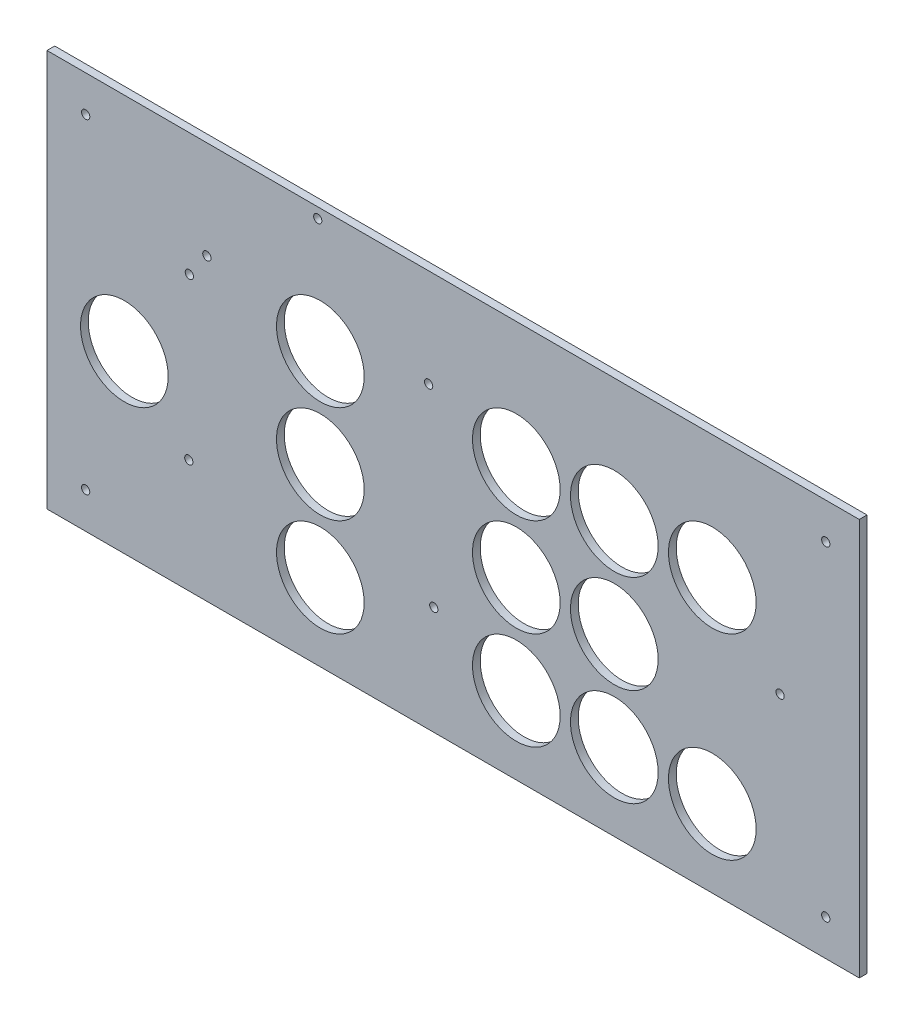
SolidWorks part; units mm, degrees
ref_plane "前视基准面" through (0, 0, 0) normal (0, 0, 1) x (1, 0, 0)
ref_plane "上视基准面" through (0, 0, 0) normal (0, 1, 0) x (1, 0, 0)
ref_plane "右视基准面" through (0, 0, 0) normal (1, 0, 0) x (0, 0, -1)
other "Configuration Table"
sketch "草图1" plane through (0, 0, 0) normal (0, 0, 1) x (1, 0, 0)
  line L1 (-150, -42) -> (165, -42)
  line L2 (-150, -42) -> (-150, 112)
  line L3 (-150, 112) -> (165, 112)
  line L4 (165, -42) -> (165, 112)
  line L5 (-150, -42) -> (165, 112) construction
  line L6 (-150, 112) -> (165, -42) construction
  circle A0 centre (0, 0) radius 1.6
  circle A1 centre (-94.8, 64.4) radius 1.6
  circle A2 centre (134.3, 38) radius 1.6
  circle A3 centre (-95, 2) radius 1.6
  circle A4 centre (-88, 74) radius 1.6
  circle A5 centre (-2, 74) radius 1.6
  circle A6 centre (-45, 108) radius 1.6
  circle A7 centre (-135, -28) radius 1.6
  circle A8 centre (152, -28) radius 1.6
  circle A9 centre (-135, 98) radius 1.6
  circle A10 centre (152, 98) radius 1.6
  circle A11 centre (-120, 26) radius 17
  circle A12 centre (-44, -12) radius 17
  circle A13 centre (-44, 26) radius 17
  circle A14 centre (-44, 64) radius 17
  circle A15 centre (32, -12) radius 17
  circle A16 centre (32, 26) radius 17
  circle A17 centre (32, 64) radius 17
  circle A18 centre (70, -12) radius 17
  circle A19 centre (70, 26) radius 17
  circle A20 centre (70, 64) radius 17
  circle A21 centre (108, -12) radius 17
  circle A22 centre (108, 64) radius 17
  point P0 (7.5, 35)
extrude "凸台-拉伸1" add sketch "草图1" along normal mid plane 3
